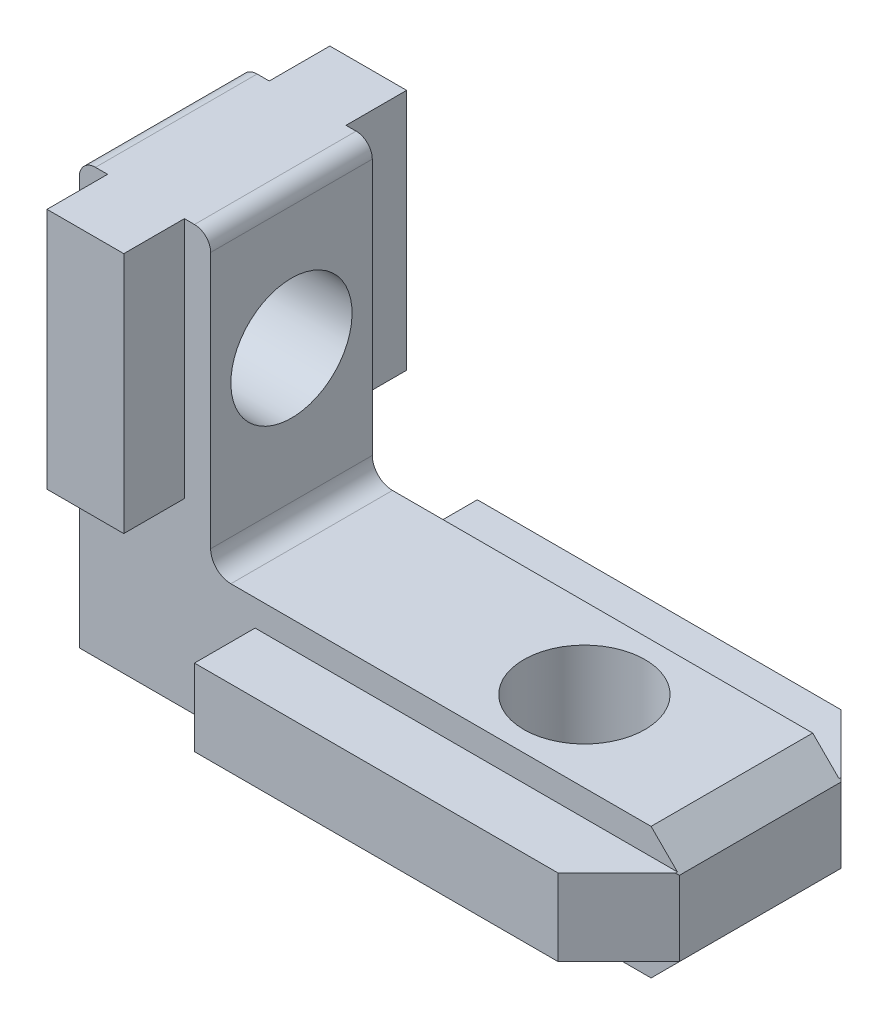
SolidWorks part; units mm, degrees
ref_plane "Спереди" through (0, 0, 0) normal (0, 0, 1) x (1, 0, 0)
ref_plane "Сверху" through (0, 0, 0) normal (0, 1, 0) x (1, 0, 0)
ref_plane "Справа" through (0, 0, 0) normal (1, 0, 0) x (0, 0, -1)
sketch "Sketch1" plane through (0, 0, 0) normal (0, 0, 1) x (1, 0, 0)
  line L0 (0, 0) -> (0, 14.5)
  line L1 (0, 14.5) -> (-6.5, 14.5)
  line L2 (-6.5, 14.5) -> (-6.5, -6.5)
  line L3 (-6.5, -6.5) -> (23.2, -6.5)
  line L4 (23.2, -6.5) -> (23.2, 0)
  line L5 (23.2, 0) -> (0, 0)
  dimension "D1" = 6.5
  dimension "D2" = 6.5
  dimension "D3" = 21
  dimension "D4" = 29.7
extrude "Extrude1" add sketch "Sketch1" along normal blind 4 and the other way blind 4
sketch "Sketch2" plane through (0, 0, 4) normal (0, 0, 1) x (1, 0, 0)
  line L0 (0, 14.5) -> (-6.5, 14.5) construction
  line L1 (-5.1, 14.5) -> (-1.3, 14.5)
  line L2 (-5.1, 14.5) -> (-5.1, 2.5)
  line L3 (-5.1, 2.5) -> (-1.3, 2.5)
  line L4 (-1.3, 14.5) -> (-1.3, 2.5)
  line L6 (23.2, -5.1) -> (2.2, -5.1)
  line L7 (23.2, -5.1) -> (23.2, -1.3)
  line L8 (23.2, -1.3) -> (2.2, -1.3)
  line L9 (2.2, -5.1) -> (2.2, -1.3)
  line L11 (-6.5, 14.5) -> (-6.5, -6.5) construction
  line L13 (-6.5, -6.5) -> (23.2, -6.5) construction
  dimension "D1" = 12
  dimension "D2" = 3.8
  dimension "D3" = 3.8
  dimension "D4" = 1.4
  dimension "D5" = 21
  dimension "D6" = 1.4
extrude "Extrude2" add sketch "Sketch2" along normal blind 3
chamfer "Chamfer1" distance 3 angle 45 1 edges at (23.2, -3.2, 7)
mirror "Mirror1" about plane through (0, 0, 0) normal (0, 0, 1) of "Extrude2", "Chamfer1"
chamfer "Chamfer2" distance 1.4 angle 45 2 edges at (23.2, -6.5, 0) (23.2, 0, 0)
sketch "Sketch4" plane through (0, 0, 0) normal (0, 1, 0) x (1, 0, 0)
  circle A0 centre (14.5, 0) radius 3
  dimension "D1" = 6
  dimension "D2" = 21
extrude "Extrude3" cut sketch "Sketch4" against normal up to next
ref_plane "Plane1" through (0, 0, 0) normal (0.7071, -0.7071, 0) x (0, 0, -1)
fillet "Fillet1" radius 0.8 2 edges at (-6.5, 14.5, 0) (0, 14.5, 0)
sketch "Sketch5" plane through (0, 0, 0) normal (1, 0, 0) x (0, 0, -1)
  line L0 (-7, 14.5) -> (-4, 14.5) construction
  circle A0 centre (0, 7.6) radius 3
  dimension "D1" = 6
  dimension "D2" = 6.9
extrude "Extrude4" cut sketch "Sketch5" against normal up to next
fillet "Fillet2" radius 1 1 edges at (0, 0, 0)
